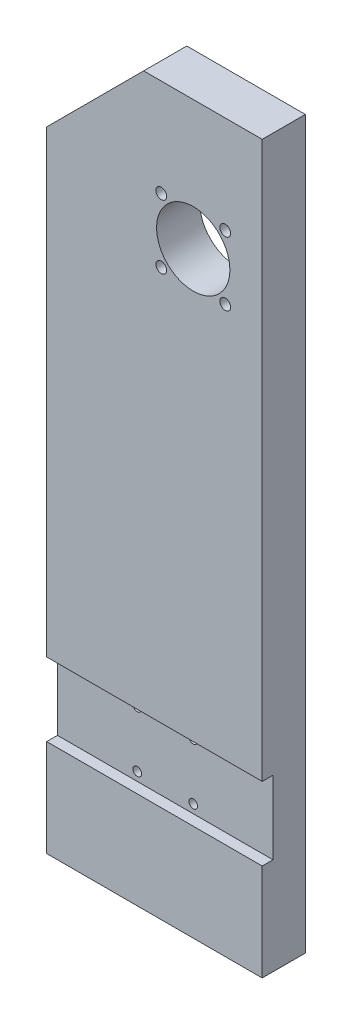
SolidWorks part; units mm, degrees
ref_plane "Front Plane" through (0, 0, 0) normal (0, 0, 1) x (1, 0, 0)
ref_plane "Top Plane" through (0, 0, 0) normal (0, 1, 0) x (1, 0, 0)
ref_plane "Right Plane" through (0, 0, 0) normal (1, 0, 0) x (0, 0, -1)
sketch "Sketch1" plane through (0, 0, 0) normal (0, 0, 1) x (1, 0, 0)
  line L0 (65.7045, 560.5004) -> (50.8553, 575.3496) construction
  line L1 (65.7045, 560.5004) -> (44.7045, 560.5004) construction
  line L2 (65.7045, 560.5004) -> (65.7045, 581.5004) construction
  line L3 (47.7045, 545.8558) -> (47.7045, 439.2537) construction
  line L4 (7.7288, 345.5004) -> (63.5732, 345.5004) construction
  line L5 (97.7045, 283.5004) -> (-2.2955, 283.5004)
  line L6 (97.7045, 283.5004) -> (97.7045, 620.5004)
  line L7 (97.7045, 620.5004) -> (-2.2955, 620.5004)
  line L8 (-2.2955, 283.5004) -> (-2.2955, 620.5004)
  line L9 (97.7045, 283.5004) -> (-2.2955, 620.5004) construction
  line L10 (97.7045, 620.5004) -> (-2.2955, 283.5004) construction
  circle A0 centre (65.7045, 560.5004) radius 17
  circle A1 centre (65.7045, 560.5004) radius 21 construction
  circle A2 centre (80.5538, 575.3496) radius 2.5
  circle A3 centre (80.5538, 545.6511) radius 2.5
  circle A4 centre (50.8553, 545.6511) radius 2.5
  circle A5 centre (50.8553, 575.3496) radius 2.5
  circle A6 centre (34.7045, 358.5004) radius 2
  circle A7 centre (60.7045, 358.5004) radius 2
  circle A8 centre (60.7045, 332.5004) radius 2
  circle A9 centre (34.7045, 332.5004) radius 2
  point P5 (50.8553, 575.3496)
  point P6 (80.5538, 575.3496)
  point P7 (80.5538, 545.6511)
  point P8 (50.8553, 545.6511)
  point P19 (47.7045, 452.0004)
  dimension "D2" = 5
  dimension "D3" = 34
  dimension "D4" = 42
  dimension "D10" = 4
  dimension "D1" = 45
  dimension "D5" = 337
  dimension "D6" = 100
  dimension "D7" = 60
  dimension "D8" = 13
  dimension "D9" = 13
  dimension "D11" = 62
  dimension "D12" = 32
extrude "Boss-Extrude1" add sketch "Sketch1" along normal blind 20
chamfer "Chamfer1" distance 45 angle 45 1 edges at (-2.2955, 620.5004, 10)
sketch "Sketch2" plane through (0, 0, 20) normal (0, 0, 1) x (1, 0, 0)
  line L0 (60.7045, 358.5004) -> (34.7045, 332.5004) construction
  line L1 (34.7045, 358.5004) -> (60.7045, 332.5004) construction
  line L3 (97.7045, 328.5004) -> (-2.2955, 328.5004)
  line L4 (97.7045, 328.5004) -> (97.7045, 362.5004)
  line L5 (97.7045, 362.5004) -> (-2.2955, 362.5004)
  line L6 (-2.2955, 328.5004) -> (-2.2955, 362.5004)
  line L7 (97.7045, 328.5004) -> (-2.2955, 362.5004) construction
  line L8 (97.7045, 362.5004) -> (-2.2955, 328.5004) construction
  point P8 (47.7045, 345.5004)
  point P9 (47.7045, 345.5004)
  dimension "D1" = 100
  dimension "D2" = 34
extrude "Cut-Extrude1" cut sketch "Sketch2" against normal blind 5
